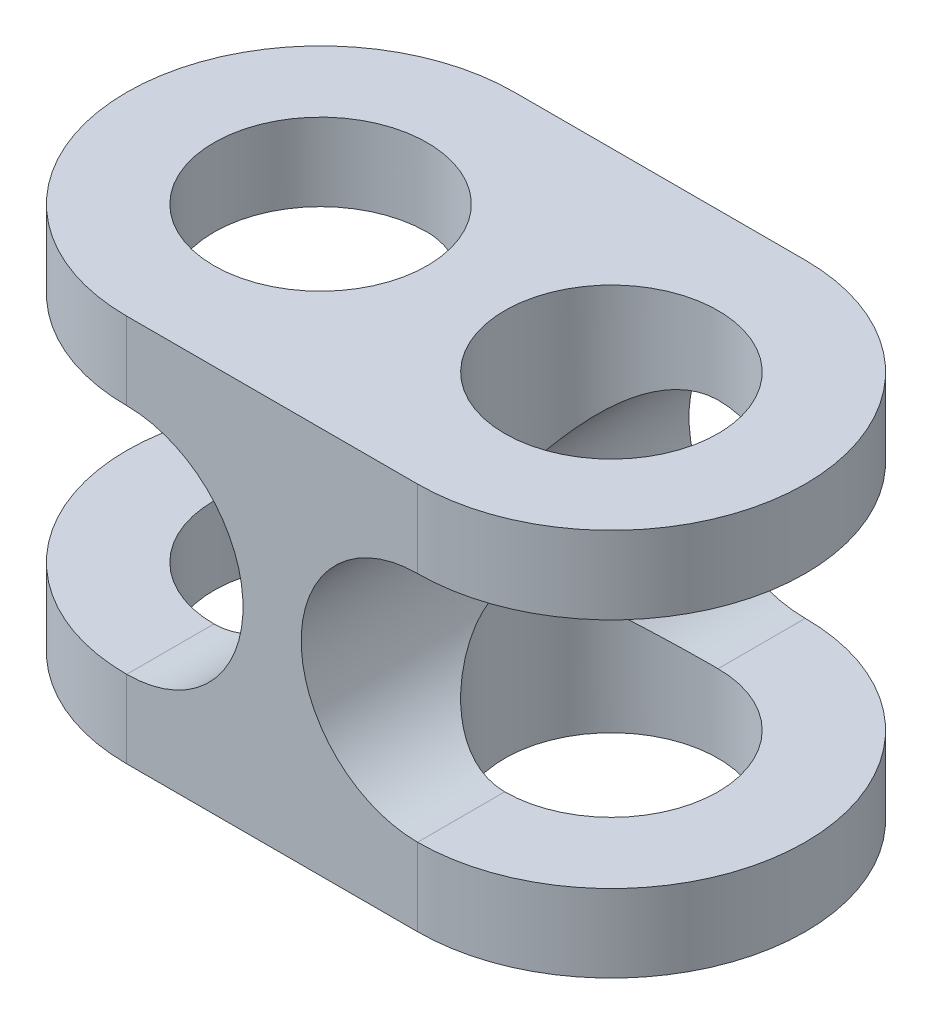
SolidWorks part; units mm, degrees
ref_plane "Front Plane" through (0, 0, 0) normal (0, 0, 1) x (1, 0, 0)
ref_plane "Top Plane" through (0, 0, 0) normal (0, 1, 0) x (1, 0, 0)
ref_plane "Right Plane" through (0, 0, 0) normal (1, 0, 0) x (0, 0, -1)
sketch "Sketch1" plane through (0, 0, 0) normal (0, 1, 0) x (1, 0, 0)
  line L0 (0, 0) -> (7.5, 0) construction
  line L1 (0, 5) -> (7.5, 5)
  line L2 (0, -5) -> (7.5, -5)
  line L3 (7.5, 5) -> (7.5, -5) construction
  line L4 (0, 5) -> (0, -5) construction
  arc A0 (0, 5) -> (0, -5) centre (0, 0) ccw
  arc A1 (7.5, -5) -> (7.5, 5) centre (7.5, 0) ccw
  circle A2 centre (0, 0) radius 2.75
  circle A3 centre (7.5, 0) radius 2.75
  dimension "D2" = 10
  dimension "D3" = 10
  dimension "D4" = 5.5
  dimension "D5" = 5.5
  dimension "D1" = 7.5
extrude "Boss-Extrude1" add sketch "Sketch1" along normal blind 10
sketch "Sketch2" plane through (0, 0, 0) normal (0, 0, 1) x (1, 0, 0)
  line L0 (0, 0) -> (0, 10) construction
  line L1 (7.5, 0) -> (7.5, 10) construction
  line L2 (0, 8) -> (-5, 8)
  line L3 (-5, 10) -> (-5, 0) construction
  line L4 (-5, 8) -> (-5, 2)
  line L5 (-5, 2) -> (0, 2)
  line L6 (7.5, 8) -> (12.5, 8)
  line L7 (12.5, 0) -> (12.5, 10) construction
  line L8 (12.5, 8) -> (12.5, 2)
  line L9 (12.5, 2) -> (7.5, 2)
  arc A0 (0, 8) -> (0, 2) centre (0, 5) cw
  arc A1 (7.5, 8) -> (7.5, 2) centre (7.5, 5) ccw
  dimension "D1" = 3
  dimension "D2" = 3
extrude "Cut-Extrude1" cut sketch "Sketch2" against normal up to next and the other way up to next
